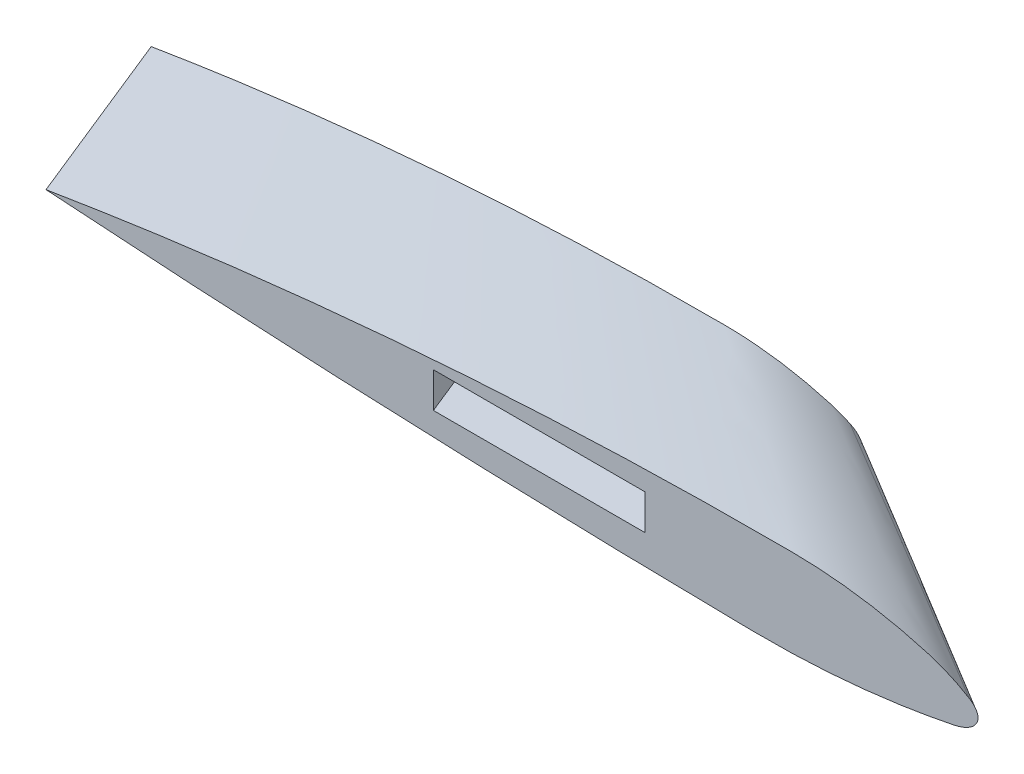
SolidWorks part; units mm, degrees
material "EPS 1.5lb"
ref_plane "Front Plane" through (0, 0, 0) normal (0, 0, 1) x (1, 0, 0)
ref_plane "Top Plane" through (0, 0, 0) normal (0, 1, 0) x (1, 0, 0)
ref_plane "Right Plane" through (0, 0, 0) normal (1, 0, 0) x (0, 0, -1)
sketch "Sketch1" plane through (0, 0, 0) normal (0, 0, 1) x (1, 0, 0)
  ellipse E1 centre (30.4917, -1212.2061) end of major axis (1372.9244, -1212.2061) minor radius 1244.6819 (36.9797, 32.4612) -> (-204.2943, 13.2914) ccw
  ellipse E3 centre (36.2563, -106.312) end of major axis (185.9298, -106.312) minor radius 138.7748 (81.5372, 25.9598) -> (36.9797, 32.4612) ccw
  ellipse E5 centre (65.7891, -20.0426) end of major axis (117.8436, -20.0426) minor radius 48.2641 (103.4339, 13.2914) -> (81.5372, 25.9598) ccw
  ellipse E7 centre (28.1769, 268.4704) end of major axis (313.5001, 268.4704) minor radius 264.5471 (24.2792, 3.948) -> (103.4339, 13.2914) ccw
  ellipse E9 centre (66.1797, 2847.5869) end of major axis (3464.1974, 2820.9695) minor radius 2843.9273 (-204.2943, 13.2914) -> (24.2792, 3.948) ccw
ref_plane "Plane1" through (0, 0, -57.15) normal (0, 0, 1) x (1, 0, 0)
sketch "Sketch2" plane through (0, 0, -57.15) normal (0, 0, 1) x (1, 0, 0)
  ellipse E1 centre (-46.6002, -930.3417) end of major axis (-1080.2734, -930.3417) minor radius 958.4051 (-41.6044, 28.0522) -> (-227.3854, 13.2914) ccw
  ellipse E3 centre (-42.1614, -78.8032) end of major axis (-157.41, -78.8032) minor radius 106.8566 (-7.2952, 23.0461) -> (-41.6044, 28.0522) ccw
  ellipse E5 centre (-19.4212, -12.3758) end of major axis (20.6607, -12.3758) minor radius 37.1633 (9.5653, 13.2914) -> (-7.2952, 23.0461) ccw
  ellipse E7 centre (-48.3826, 209.7792) end of major axis (171.3163, 209.7792) minor radius 203.7012 (-51.3838, 6.097) -> (9.5653, 13.2914) ccw
  ellipse E9 centre (-19.1204, 2195.6989) end of major axis (2597.3532, 2175.2036) minor radius 2189.824 (-227.3854, 13.2914) -> (-51.3838, 6.097) ccw
loft "Loft1" add profiles "Sketch1", "Sketch2" connector at (-204.2943, 13.2914, 0) connector at (-227.3854, 13.2914, -57.15)
fillet "Fillet1" radius 6.35 1 edges
ref_plane "Plane2" through (0, 19.812, 0) normal (0, 1, 0) x (1, 0, 0)
sketch "Sketch5" plane through (0, 19.812, 0) normal (0, 1, 0) x (1, 0, 0)
  line L1 (-33.4554, 57.15) -> (-10.3653, 0)
  line L2 (-10.3653, 0) -> (-78.8522, 0)
  line L3 (-78.8522, 0) -> (-101.9423, 57.15)
  line L4 (-101.9423, 57.15) -> (-33.4554, 57.15)
  line L5 (-15.7361, 0) -> (15.7361, 0) construction
  line L6 (-15.7361, 57.15) -> (15.7361, 57.15) construction
  line L7 (-67.6988, 57.15) -> (-44.6087, 0) construction
  dimension "D1" = 68
  dimension "D2" = 159.6855
  dimension "D3" = 63.5
extrude "Cut-Extrude1" cut sketch "Sketch5" against normal mid plane 11.43
